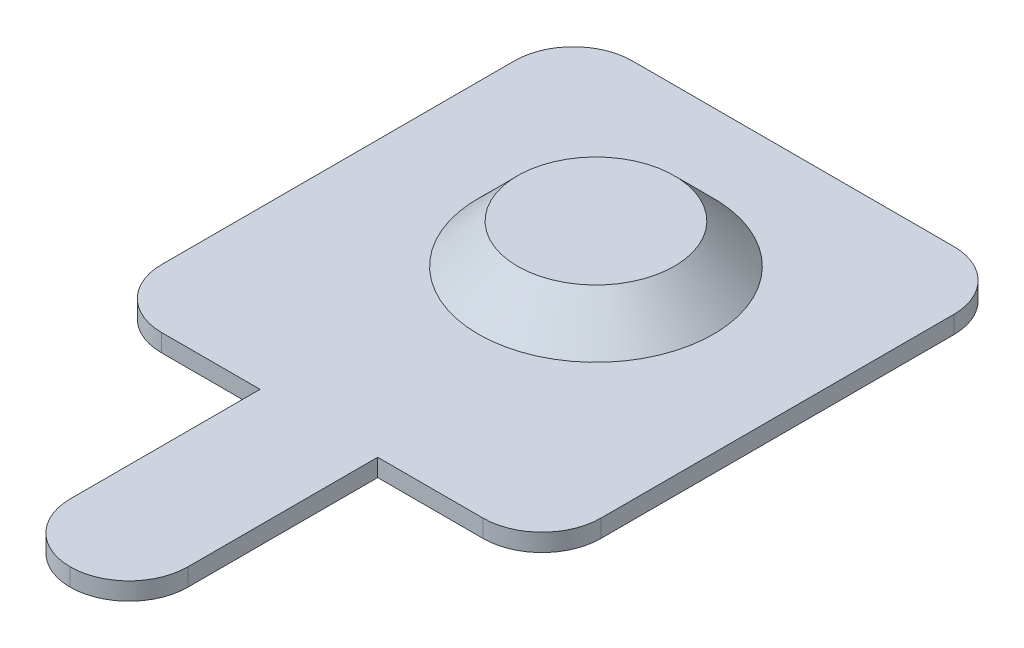
SolidWorks part; units mm, degrees
ref_plane "Front Plane" through (0, 0, 0) normal (0, 0, 1) x (1, 0, 0)
ref_plane "Top Plane" through (0, 0, 0) normal (0, 1, 0) x (1, 0, 0)
ref_plane "Right Plane" through (0, 0, 0) normal (1, 0, 0) x (0, 0, -1)
sketch "Sketch1" plane through (0, 0, 0) normal (0, 1, 0) x (1, 0, 0)
  line L0 (5.6, 12) -> (5.6, 0) construction
  line L1 (0, 0) -> (11.2, 0)
  line L2 (0, 0) -> (0, 12)
  line L3 (0, 12) -> (11.2, 12)
  line L4 (11.2, 0) -> (11.2, 12)
  line L5 (4.0097, 0) -> (7.0097, 0)
  line L6 (4.0097, 0) -> (4.0097, -6.34)
  line L7 (4.0097, -6.34) -> (7.0097, -6.34)
  line L8 (7.0097, 0) -> (7.0097, -6.34)
  line L9 (5.5097, -6.34) -> (5.5097, 0) construction
  dimension "D1" = 12
  dimension "D2" = 11.2
  dimension "D3" = 3
  dimension "D4" = 18.34
extrude "Boss-Extrude1" add sketch "Sketch1" along normal blind 0.45 contours L1 L4 L3 L2 | L8 L1 L6 L7 region at (5.6, 0, -6) region at (5.5097, 0, 3.17)
fillet "Fillet1" radius 1.5 6 edges at (0, 0.225, 0) (0, 0.225, -12) (11.2, 0.225, -12) (11.2, 0.225, 0) (7.0097, 0.225, 6.34) (4.0097, 0.225, 6.34)
sketch "Sketch2" plane through (0, 0.45, 0) normal (0, 1, 0) x (1, 0, 0)
  line L0 (1.5, 12) -> (9.7, 12) construction
  line L1 (5.6, 12) -> (5.5097, -6.34) construction
  circle A0 centre (5.5754, 7) radius 2
  dimension "D1" = 4
  dimension "D2" = 5
extrude "Boss-Extrude2" add sketch "Sketch2" along normal blind 1
chamfer "Chamfer1" distance 1 angle 45 1 edges at (5.5754, 0.45, -5)
